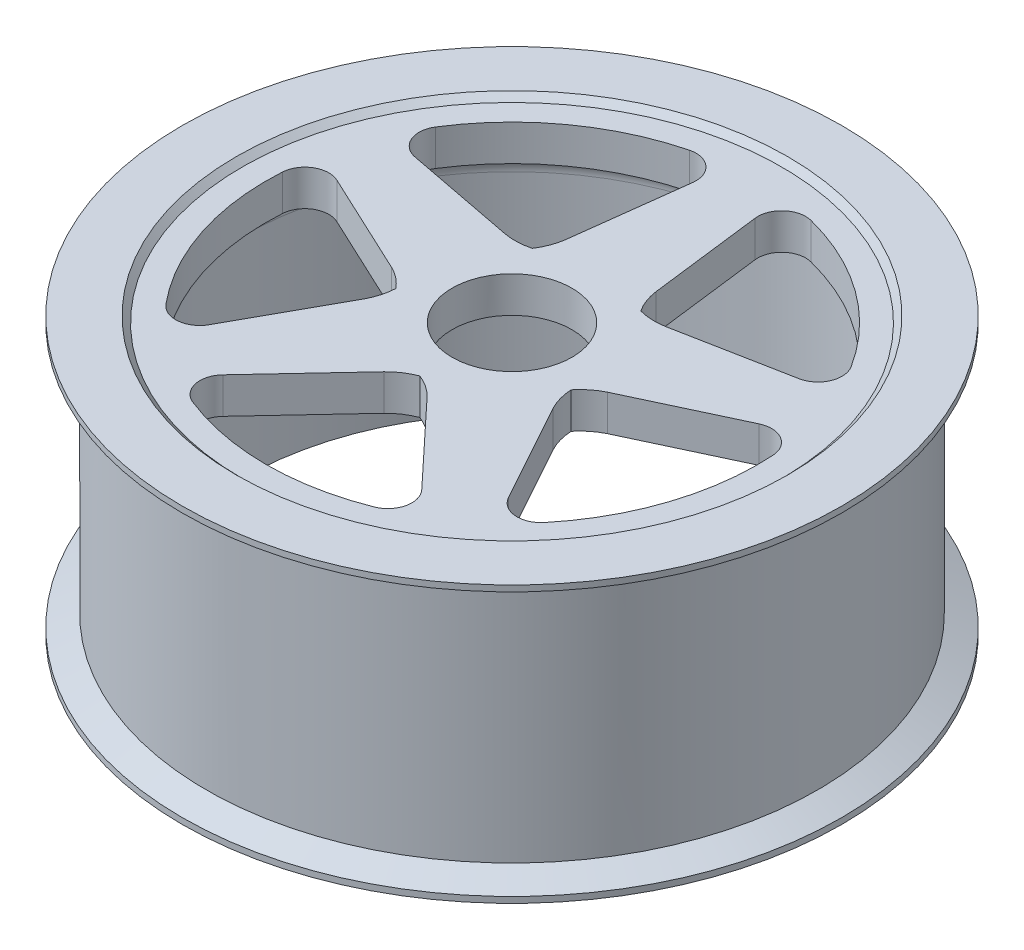
SolidWorks part; units mm, degrees
ref_plane "Front Plane" through (0, 0, 0) normal (0, 0, 1) x (1, 0, 0)
ref_plane "Top Plane" through (0, 0, 0) normal (0, 1, 0) x (1, 0, 0)
ref_plane "Right Plane" through (0, 0, 0) normal (1, 0, 0) x (0, 0, -1)
sketch "Sketch1" plane through (0, 0, 0) normal (0, 1, 0) x (1, 0, 0)
  line L0 (3.7078, 1.75) -> (3.7078, -1.75)
  line L1 (0, -55) -> (0, 55) construction
  line L2 (-3.7078, 1.75) -> (-3.7078, -1.75)
  circle A0 centre (0, 0) radius 4.1
  circle A1 centre (0, 0) radius 25.5
  dimension "D1" = 8.2
  dimension "D3" = 51
  dimension "D2" = 3.5
extrude "Boss-Extrude1" add sketch "Sketch1" along normal blind 4.5 contours A1 A0 | L2 A0 | L0 A0 region at (3.8653, 0, 0) region at (-3.8653, 0, 0) region at (-24.7788, 0, 0)
sketch "Sketch2" plane through (0, 4.5, 0) normal (0, 1, 0) x (1, 0, 0)
  line L0 (0, 7.5) -> (0, 22.5)
  line L1 (7.1329, 2.3176) -> (21.3988, 6.9529)
  line L2 (4.4084, -6.0676) -> (13.2252, -18.2029)
  line L3 (-4.4084, -6.0676) -> (-13.2252, -18.2029)
  line L4 (-7.1329, 2.3176) -> (-21.3988, 6.9529)
  line L5 (-2, 22.4109) -> (-4, 6.3443)
  line L6 (2, 22.4109) -> (4, 6.3443)
  line L7 (20.696, 8.8275) -> (4.7977, 5.7647)
  line L8 (21.9321, 5.0232) -> (7.2698, -1.8437)
  line L9 (14.7909, -16.9553) -> (6.9651, -2.7815)
  line L10 (11.5548, -19.3064) -> (0.493, -7.4838)
  line L11 (-11.5548, -19.3064) -> (-0.493, -7.4838)
  line L12 (-14.7909, -16.9553) -> (-6.9651, -2.7815)
  line L13 (-21.9321, 5.0232) -> (-7.2698, -1.8437)
  line L14 (-20.696, 8.8275) -> (-4.7977, 5.7647)
  circle A0 centre (0, 0) radius 7.5
  circle A1 centre (0, 0) radius 22.5
  arc A2 (-3.3596, 22.2478) -> (-2.1729, 21.0218) centre (-3.3793, 21.0414) cw
  arc A3 (3.3596, 22.2478) -> (2.1729, 21.0218) centre (3.3793, 21.0414) ccw
  arc A4 (-3.7646, 8.2353) -> (-5.0228, 5.5697) centre (-8.7144, 8.9419) cw
  arc A5 (3.7646, 8.2353) -> (5.0228, 5.5697) centre (8.7144, 8.9419) ccw
  arc A6 (20.1207, 10.0701) -> (19.3214, 8.5627) centre (18.9673, 9.716) cw
  arc A7 (22.1971, 3.6798) -> (20.6644, 4.4295) centre (21.0558, 3.2883) ccw
  arc A8 (6.6689, 6.1252) -> (3.7449, 6.4981) centre (5.8114, 11.0511) cw
  arc A9 (8.9956, -1.0355) -> (6.8492, -3.0559) centre (11.1972, -5.5247) ccw
  arc A10 (15.7949, -16.0241) -> (14.1142, -15.7298) centre (15.1017, -15.0366) cw
  arc A11 (10.3589, -19.9735) -> (10.5984, -18.2842) centre (9.634, -19.0092) ccw
  arc A12 (7.8862, -4.4497) -> (7.3373, -1.5536) centre (12.306, -2.112) cw
  arc A13 (1.795, -8.8753) -> (-0.7898, -7.4583) centre (-1.7942, -12.3564) ccw
  arc A14 (-10.3589, -19.9735) -> (-10.5984, -18.2842) centre (-9.634, -19.0092) cw
  arc A15 (-15.7949, -16.0241) -> (-14.1142, -15.7298) centre (-15.1017, -15.0366) ccw
  arc A16 (-1.795, -8.8753) -> (0.7898, -7.4583) centre (1.7942, -12.3564) cw
  arc A17 (-7.8862, -4.4497) -> (-7.3373, -1.5536) centre (-12.306, -2.112) ccw
  arc A18 (-22.1971, 3.6798) -> (-20.6644, 4.4295) centre (-21.0558, 3.2883) cw
  arc A19 (-20.1207, 10.0701) -> (-19.3214, 8.5627) centre (-18.9673, 9.716) ccw
  arc A20 (-8.9956, -1.0355) -> (-6.8492, -3.0559) centre (-11.1972, -5.5247) cw
  arc A21 (-6.6689, 6.1252) -> (-3.7449, 6.4981) centre (-5.8114, 11.0511) ccw
  point P16 (0, 0)
  point P98 (0, 0)
  dimension "D1" = 15
  dimension "D2" = 45
  dimension "D8" = 5
  dimension "D4" = 2
  dimension "D5" = 2
  dimension "D6" = 4
  dimension "D7" = 4
  dimension "D3" = 5
extrude "Cut-Extrude1" cut sketch "Sketch2" against normal up to surface (4.5 mm away) contours L14 A21 A4 L5 A2 A1 A19 | A8 L7 A6 A1 A3 L6 A5 | A20 L13 A18 A1 A15 L12 A17 | A12 L9 A10 A1 A7 L8 A9 | A16 L11 A14 A1 A11 L10 A13 region at (9.7699, 4.5, -13.4471) region at (-9.7699, 4.5, -13.4471) region at (15.808, 4.5, 5.1363) region at (-15.808, 4.5, 5.1363) region at (0, 4.5, 16.6216) up to face at (0, 0, 0)
sketch "Sketch3" plane through (0, 4.5, 0) normal (0, 1, 0) x (1, 0, 0)
  circle A0 centre (0, 0) radius 27.5
  circle A1 centre (0, 0) radius 25.5
  dimension "D1" = 55
extrude "Boss-Extrude2" add sketch "Sketch3" against normal blind 1.5
sketch "Sketch4" plane through (0, 0, 0) normal (0, -1, 0) x (1, 0, 0)
  circle A0 centre (0, 0) radius 25.5
  circle A1 centre (0, 0) radius 22.5
extrude "Boss-Extrude3" add sketch "Sketch4" along normal blind 18.5
sketch "Sketch5" plane through (0, -18.5, 0) normal (0, -1, 0) x (1, 0, 0)
  circle A0 centre (0, 0) radius 27.5
  circle A1 centre (0, 0) radius 25.5
  dimension "D1" = 55
extrude "Boss-Extrude4" add sketch "Sketch5" against normal blind 1.5
chamfer "Chamfer1" distance 2 angle 26.565 2 edges at (0, -17, -27.5) (0, 3, 27.5) first distance on face at (0, -17, -25.5) first distance on face at (0, 3, 25.5)
sketch "Sketch6" plane through (0, 4.5, 0) normal (0, 1, 0) x (1, 0, 0)
  circle A0 centre (0, 0) radius 5
  dimension "D1" = 10
extrude "Cut-Extrude2" cut sketch "Sketch6" against normal up to surface (4.5 mm away) up to face at (0, 0, 0)
sketch "Sketch7" plane through (0, 0, 0) normal (0, -1, 0) x (1, 0, 0)
  circle A0 centre (0, 0) radius 22.5
extrude "Cut-Extrude3" cut sketch "Sketch7" against normal blind 1
sketch "Sketch8" plane through (0, 4.5, 0) normal (0, 1, 0) x (1, 0, 0)
  circle A0 centre (0, 0) radius 22.5
extrude "Cut-Extrude4" cut sketch "Sketch8" against normal blind 0.5
sketch "Sketch9" plane through (0, 4, 0) normal (0, 1, 0) x (1, 0, 0)
  circle A0 centre (0, 0) radius 20.5
  arc A1 (-20.1207, 10.0701) -> (-22.1971, 3.6798) centre (0, 0) ccw construction
  circle A2 centre (0, 0) radius 22.5
  arc M4 (-19.3214, 8.5627) -> (-20.1207, 10.0701) centre (-18.9673, 9.716) cw
  arc M5 (-20.1207, 10.0701) -> (-22.1971, 3.6798) centre (0, 0) ccw
  arc M6 (-22.1971, 3.6798) -> (-20.6644, 4.4295) centre (-21.0558, 3.2883) cw
  line M7 (-20.6644, 4.4295) -> (-8.9956, -1.0355)
  line M10 (-7.8862, -4.4497) -> (-14.1142, -15.7298)
  arc M11 (-14.1142, -15.7298) -> (-15.7949, -16.0241) centre (-15.1017, -15.0366) cw
  arc M12 (-15.7949, -16.0241) -> (-10.3589, -19.9735) centre (0, 0) ccw
  arc M13 (-10.3589, -19.9735) -> (-10.5984, -18.2842) centre (-9.634, -19.0092) cw
  line M14 (-10.5984, -18.2842) -> (-1.795, -8.8753)
  line M17 (1.795, -8.8753) -> (10.5984, -18.2842)
  arc M18 (10.5984, -18.2842) -> (10.3589, -19.9735) centre (9.634, -19.0092) cw
  arc M20 (15.7949, -16.0241) -> (14.1142, -15.7298) centre (15.1017, -15.0366) cw
  line M21 (14.1142, -15.7298) -> (7.8862, -4.4497)
  line M24 (8.9956, -1.0355) -> (20.6644, 4.4295)
  arc M25 (20.6644, 4.4295) -> (22.1971, 3.6798) centre (21.0558, 3.2883) cw
  arc M26 (22.1971, 3.6798) -> (20.1207, 10.0701) centre (0, 0) ccw
  arc M27 (20.1207, 10.0701) -> (19.3214, 8.5627) centre (18.9673, 9.716) cw
  line M28 (19.3214, 8.5627) -> (6.6689, 6.1252)
  line M31 (3.7646, 8.2353) -> (2.1729, 21.0218)
  arc M32 (2.1729, 21.0218) -> (3.3596, 22.2478) centre (3.3793, 21.0414) cw
  arc M33 (3.3596, 22.2478) -> (-3.3596, 22.2478) centre (0, 0) ccw
  arc M34 (-3.3596, 22.2478) -> (-2.1729, 21.0218) centre (-3.3793, 21.0414) cw
  line M35 (-2.1729, 21.0218) -> (-3.7646, 8.2353)
  line M38 (-6.6689, 6.1252) -> (-19.3214, 8.5627)
  dimension "D1" = 2
extrude "Boss-Extrude5" add sketch "Sketch9" against normal blind 3 contours A2 A0 M6 M11 M10 M7 | A2 A0 M34 M4 M38 M35 | A2 A0 M27 M32 M31 M28 | A2 A0 M20 M25 M24 M21 | A2 A0 M13 M18 M17 M14 | A0 M10 M11 M12 M13 M14 | A0 M38 M4 M5 M6 M7 | A0 M31 M32 M33 M34 M35 | A0 M24 M25 M26 M27 M28 region at (19.5548, 4, 6.3537) region at (20.4558, 4, -6.6465) region at (12.0855, 4, -16.6343) region at (0, 4, 20.5611) region at (0, 4, -21.5085) region at (-12.6424, 4, 17.4007) region at (-12.0855, 4, -16.6343) region at (-19.5548, 4, 6.3537) region at (-20.4558, 4, -6.6465)
fillet "Fillet1" radius 2 10 edges at (-10.1536, 2.5, 17.8088) (10.1536, 2.5, 17.8088) (13.7996, 2.5, 15.1599) (20.0748, 2.5, -4.1534) (18.6822, 2.5, -8.4395) (2.2533, 2.5, -20.3758) (-18.6822, 2.5, -8.4395) (-2.2533, 2.5, -20.3758) (-13.7996, 2.5, 15.1599) (-20.0748, 2.5, -4.1534)
chamfer "Chamfer2" distance 0.5 angle 45 1 edges at (0, 4.5, 22.5)
fillet "Fillet2" radius 2 1 edges at (0, 1, -22.5)
